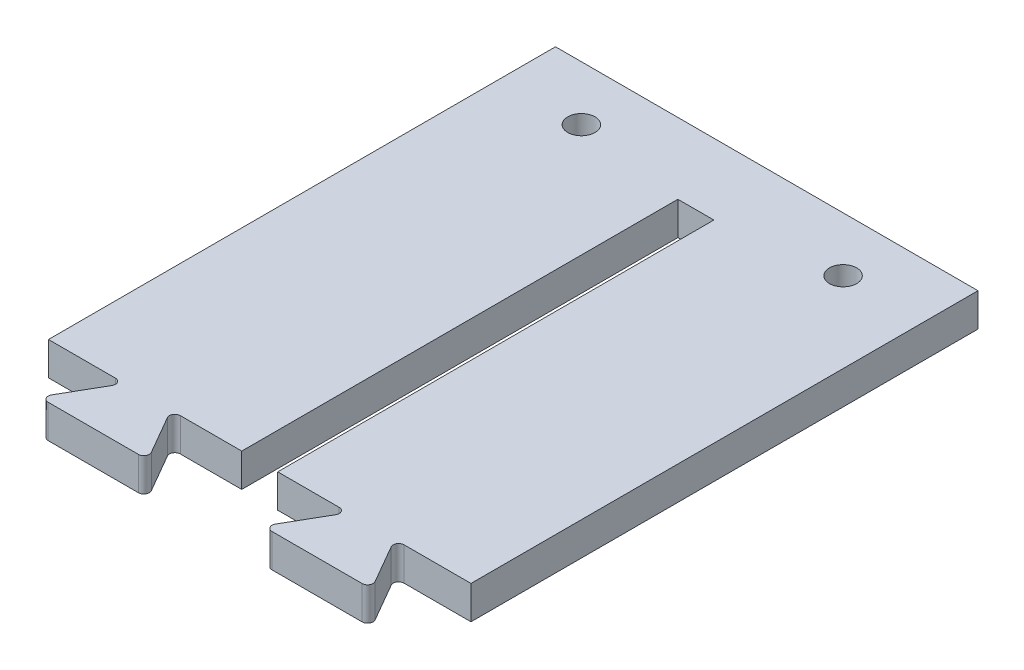
SolidWorks part; units mm, degrees
ref_plane "Front Plane" through (0, 0, 0) normal (0, 0, 1) x (1, 0, 0)
ref_plane "Top Plane" through (0, 0, 0) normal (0, 1, 0) x (1, 0, 0)
ref_plane "Right Plane" through (0, 0, 0) normal (1, 0, 0) x (0, 0, -1)
sketch "Sketch1" plane through (0, 0, 0) normal (0, 1, 0) x (1, 0, 0)
  line L0 (-19.375, 0) -> (-19.375, 46.5)
  line L1 (-19.375, 46.5) -> (19.375, 46.5)
  line L2 (19.375, 46.5) -> (19.375, 0)
  line L3 (19.375, 0) -> (12.375, 0)
  line L4 (12.375, 0) -> (15.2618, -5)
  line L5 (15.2618, -5) -> (5.2618, -5)
  line L6 (5.2618, -5) -> (8.1485, 0)
  line L7 (8.1485, 0) -> (-8.1485, 0)
  line L8 (-8.1485, 0) -> (-5.2618, -5)
  line L9 (-5.2618, -5) -> (-15.2618, -5)
  line L10 (-15.2618, -5) -> (-12.375, 0)
  line L11 (-12.375, 0) -> (-19.375, 0)
  point P13 (0, 0)
  dimension "D1" = 46.5
  dimension "D2" = 38.75
  dimension "D3" = 10
  dimension "D4" = 10
  dimension "D5" = 60
  dimension "D6" = 60
  dimension "D7" = 7
  dimension "D8" = 7
  dimension "D9" = 5
  dimension "D10" = 5
extrude "Boss-Extrude1" add sketch "Sketch1" along normal blind 3.05
fillet "Fillet1" radius 0.5 8 edges at (12.375, 1.525, 0) (15.2618, 1.525, 5) (5.2618, 1.525, 5) (8.1485, 1.525, 0) (-8.1485, 1.525, 0) (-5.2618, 1.525, 5) (-15.2618, 1.525, 5) (-12.375, 1.525, 0)
sketch "Sketch3" plane through (0, 3.05, 0) normal (0, 1, 0) x (1, 0, 0)
  line L0 (0, 40) -> (0, 0) construction
  line L2 (19.375, 46.5) -> (-19.375, 46.5) construction
  line L3 (-1.65, 40) -> (1.65, 40)
  line L4 (-1.65, 40) -> (-1.65, 0)
  line L5 (-1.65, 0) -> (1.65, 0)
  line L6 (1.65, 40) -> (1.65, 0)
  line L8 (-1.65, -1.2) -> (1.65, -1.2)
  line L9 (-1.65, -1.2) -> (-1.65, -2.2)
  line L10 (-1.65, -2.2) -> (1.65, -2.2)
  line L11 (1.65, -1.2) -> (1.65, -2.2)
  point P8 (0, 40)
  point P15 (0, -1.2)
  dimension "D1" = 3.3
  dimension "D2" = 40
  dimension "D3" = 6.5
  dimension "D4" = 1.2
  dimension "D5" = 1
extrude "Cut-Extrude2" cut sketch "Sketch3" against normal through all
sketch "Sketch8" plane through (0, 3.05, 0) normal (0, 1, 0) x (1, 0, 0)
  line L0 (0, 0) -> (0, 40) construction
  line L1 (-11.2618, 37) -> (-9.2618, 37)
  line L2 (-11.2618, 37) -> (-11.2618, 3)
  line L3 (-11.2618, 3) -> (-9.2618, 3)
  line L4 (-9.2618, 37) -> (-9.2618, 3)
  line L5 (-19.375, 0) -> (-13.241, 0) construction
  line L6 (-14.3957, -5) -> (-6.1278, -5) construction
  line L8 (11.2618, 3) -> (9.2618, 3)
  line L9 (9.2618, 37) -> (9.2618, 3)
  line L10 (11.2618, 37) -> (9.2618, 37)
  line L11 (11.2618, 37) -> (11.2618, 3)
  line L12 (1.65, 40) -> (-1.65, 40) construction
  point P5 (-10.2618, -5)
  point P10 (-10.2618, 3)
  dimension "D1" = 2
  dimension "D2" = 3
  dimension "D3" = 3
extrude "Cut-Extrude3" [suppressed] cut sketch "Sketch8" against normal through all
fillet "Fillet2" [suppressed] radius 0.5
sketch "Damper Hole Locations" plane through (0, 3.05, 0) normal (0, 1, 0) x (1, 0, 0)
  line L0 (0, 40) -> (0, 0) construction
  line L3 (19.375, 46.5) -> (-19.375, 46.5) construction
  circle A0 centre (-12, 41.5) radius 1.5
  circle A1 centre (12, 41.5) radius 1.5
  dimension "D1" = 3
  dimension "D2" = 12
  dimension "D3" = 5
hole_wizard "M3 Tapped Damper Holes" positions "Sketch6" profile "Sketch7" tap size "M3x0.5" standard "ANSI Metric" end condition through all
sketch "Sketch6" plane through (0, 3.05, 0) normal (0, 1, 0) x (1, 0, 0)
  point P0 (-12, 41.5)
  point P3 (12, 41.5)
sketch "Sketch7" plane through (-12, 3.05, -41.5) normal (1, 0, 0) x (0, 0, 1)
  line L0 (0, 0) -> (0, 3.05)
  line L1 (0, 3.05) -> (1.25, 3.05)
  line L2 (1.25, 3.05) -> (1.25, 0)
  line L5 (1.25, 0) -> (0, 0)
  line L11 (0, -6.35) -> (0, 107.95) construction
  dimension "Thru Tap Drill Dia." = 2.5
  dimension "Thru Tap Drill Depth" = 3.05
cosmetic thread "Hole Thread1" parameters "D2"=3
cosmetic thread "Hole Thread2" parameters "D2"=3
sketch "Sketch9" plane through (0, 3.05, 0) normal (0, 1, 0) x (1, 0, 0)
  line L0 (-19.375, 46.5) -> (-18.875, 46.5)
  line L1 (19.375, 46.5) -> (-19.375, 46.5) construction
  line L2 (-18.875, 46.5) -> (-18.875, 0)
  line L3 (-19.375, 0) -> (-13.241, 0) construction
  line L4 (-18.875, 0) -> (-19.375, 0)
  line L5 (-19.375, 0) -> (-19.375, 46.5)
  line L6 (19.375, 46.5) -> (18.875, 46.5)
  line L7 (18.875, 46.5) -> (18.875, 0)
  line L8 (13.241, 0) -> (19.375, 0) construction
  line L9 (18.875, 0) -> (19.375, 0)
  line L10 (19.375, 0) -> (19.375, 46.5)
  dimension "D1" = 0.5
  dimension "D2" = 0.5
extrude "Cut-Extrude4" [suppressed] cut sketch "Sketch9" against normal through all
